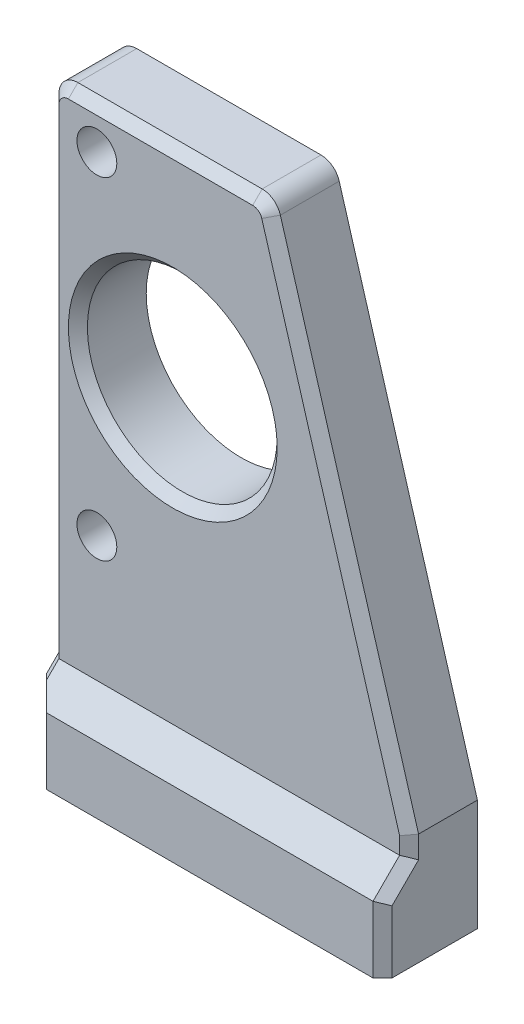
SolidWorks part; units mm, degrees
ref_plane "Ebene vorne" through (0, 0, 0) normal (0, 0, 1) x (1, 0, 0)
ref_plane "Ebene oben" through (0, 0, 0) normal (0, 1, 0) x (1, 0, 0)
ref_plane "Ebene rechts" through (0, 0, 0) normal (1, 0, 0) x (0, 0, -1)
sketch "Skizze1" plane through (0, 0, 0) normal (0, 0, 1) x (1, 0, 0)
  line L0 (0, 0) -> (71.8499, 0) construction
  line L1 (3.5487, 35) -> (89.7998, -6) construction
  line L2 (10.7739, 31.5654) -> (18.287, 47.3706) construction
  line L3 (6.9832, 42.2252) -> (14.1827, 57.3706) construction
  line L4 (14.1827, 57.3706) -> (28.287, 57.3706) construction
  line L5 (28.287, 57.3706) -> (28.287, 0)
  line L6 (28.287, 0) -> (-13.0888, 0)
  line L7 (6.9832, 42.2252) -> (0.1141, 27.7748) construction
  line L8 (0.1141, 27.7748) -> (-13.0888, 0) construction
  line L9 (-13.0888, 0) -> (-13.0888, 27.3482)
  line L10 (-13.0888, 57.3706) -> (14.1827, 57.3706) construction
  line L11 (3.5487, 35) -> (-13.0888, 42.9087) construction
  line L12 (-8.0888, 57.3706) -> (-8.0888, 15.7603) construction
  line L13 (-8.0888, 40.5319) -> (-29.0289, 40.5319) construction
  line L14 (-13.0888, 57.3706) -> (-13.0888, 62.3706)
  line L15 (-13.0888, 62.3706) -> (28.287, 62.3706)
  line L16 (28.287, 62.3706) -> (28.287, 57.3706)
  line L17 (-13.0888, 53.7156) -> (-13.0888, 27.3482)
  line L18 (-13.0888, 53.7156) -> (-13.0888, 57.3706)
  arc A0 (0, 0) -> (84.5911, 83.8491) centre (89.7998, -6) cw construction
  circle A1 centre (3.5487, 35) radius 5.5 construction
  circle A2 centre (3.5487, 35) radius 2.5 construction
  circle A3 centre (18.287, 47.3706) radius 2.25 construction
  circle A4 centre (3.2608, 15.7603) radius 2.25 construction
  arc A5 (0.1141, 27.7748) -> (6.9832, 42.2252) centre (3.5487, 35) ccw construction
  circle A7 centre (-8.0888, 23.0319) radius 2.1
  circle A8 centre (-8.0888, 58.0319) radius 2.1
  dimension "D1" = 90
  dimension "D2" = 11
  dimension "D3" = 5
  dimension "D4" = 35
  dimension "D6" = 4.5
  dimension "D12" = 4.2
  dimension "D5" = 8
  dimension "D7" = 35
  dimension "D8" = 10
  dimension "D9" = 10
  dimension "D10" = 6
  dimension "D13" = 35
  dimension "D14" = 5
  dimension "D15" = 5
extrude "Aufsatz-Linear austragen1" add sketch "Skizze1" along normal blind 10
sketch "Skizze2" plane through (0, 0, 0) normal (0, -1, 0) x (1, 0, 0)
  line L0 (-13.0888, 5) -> (28.287, 5) construction
  line L2 (28.287, 10) -> (28.287, 0) construction
  line L3 (7.5991, 5) -> (7.5991, 10) construction
  line L4 (-13.0888, 10) -> (28.287, 10) construction
  line L5 (0, 0) -> (0, 10) construction
  circle A0 centre (-7, 5) radius 1.5
  circle A2 centre (6.18, 5) radius 1.5
  circle A3 centre (19.36, 5) radius 1.5
  dimension "D1" = 3
  dimension "D2" = 7
  dimension "D3" = 6.18
  dimension "D4" = 13.18
extrude "Schnitt-Linear austragen1" cut sketch "Skizze2" against normal blind 8
sketch "Skizze4" plane through (0, 0, 10) normal (0, 0, 1) x (1, 0, 0)
  line L0 (-15.0952, 10) -> (28.287, 10)
  line L2 (28.287, 0) -> (28.287, 62.3706) construction
  line L3 (28.287, 10) -> (36.0933, 46.99)
  line L4 (36.0933, 46.99) -> (30.4291, 65.9575)
  line L5 (30.4291, 65.9575) -> (-16.081, 65.9575)
  line L6 (-16.081, 65.9575) -> (-16.081, 27.7535)
  line L7 (-16.081, 27.7535) -> (-15.0952, 10)
  line L8 (-13.0888, 0) -> (28.287, 0) construction
  dimension "D1" = 10
extrude "Schnitt-Linear austragen3" cut sketch "Skizze4" against normal blind 2.8
sketch "Skizze7" plane through (0, 0, 7.2) normal (0, 0, 1) x (1, 0, 0)
  line L0 (-8.0888, 58.0319) -> (-8.0888, 23.0319) construction
  line L1 (-8.0888, 40.5319) -> (-0.0888, 40.5319) construction
  circle A0 centre (-0.0888, 40.5319) radius 10
  dimension "D2" = 20
  dimension "D1" = 8
extrude "Schnitt-Linear austragen5" cut sketch "Skizze7" against normal through all and the other way through all
chamfer "Fase1" distance 3 angle 45 1 edges at (7.5991, 10, 10)
sketch "Skizze5" plane through (0, 0, 0) normal (0, 0, -1) x (-1, 0, 0)
  line L0 (-24.8127, 11.7368) -> (-9.8243, 62.3706)
  line L1 (-28.287, 62.3706) -> (13.0888, 62.3706) construction
  line L2 (-9.8243, 62.3706) -> (-28.287, 62.3706)
  line L3 (-28.287, 62.3706) -> (-28.287, 0)
  line L4 (-24.8127, 11.7368) -> (-24.8127, 0)
  line L5 (13.0888, 0) -> (-28.287, 0) construction
  line L6 (-24.8127, 0) -> (-28.287, 0)
extrude "Schnitt-Linear austragen4" cut sketch "Skizze5" against normal blind 10
fillet "Verrundung1" radius 2 2 edges at (-13.0888, 62.3706, 3.6) (9.8243, 62.3706, 3.6)
chamfer "Fase2" distance 1 angle 45 10 edges at (17.5305, 36.3375, 7.2) (-13.0888, 35.0853, 7.2) (9.5274, 61.973, 7.2) (-12.503, 61.7848, 7.2) (-1.3791, 62.3706, 7.2) (-13.0888, 8.4, 8.6) (24.8127, 10.7684, 7.2) (24.8127, 3.5, 10) (24.8127, 8.4, 8.6) (9.9112, 40.5319, 7.2)
chamfer "Fase3" distance 2.5 angle 45 1 edges at (-13.0888, 2.7929, 10)
sketch "Skizze8" plane through (0, 0, 0) normal (0, 0, -1) x (-1, 0, 0)
  circle A0 centre (8.0888, 23.0319) radius 3.6
  dimension "D1" = 7.2
extrude "Schnitt-Linear austragen6" cut sketch "Skizze8" against normal blind 3
